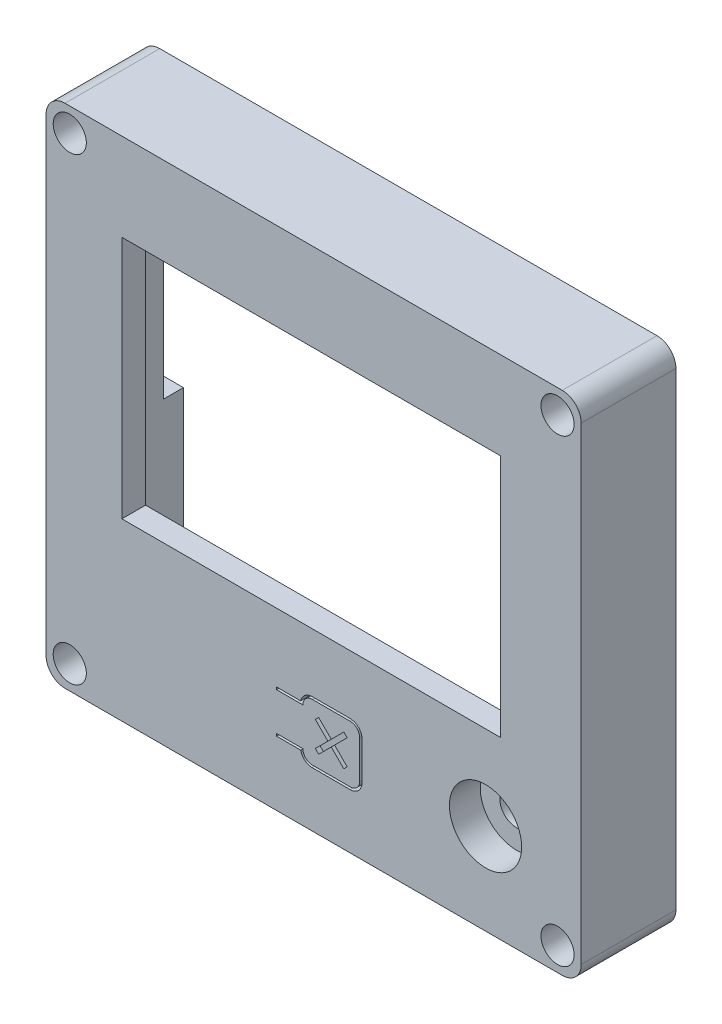
SolidWorks part; units mm, degrees
ref_plane "Front Plane" through (0, 0, 0) normal (0, 0, 1) x (1, 0, 0)
ref_plane "Top Plane" through (0, 0, 0) normal (0, 1, 0) x (1, 0, 0)
ref_plane "Right Plane" through (0, 0, 0) normal (1, 0, 0) x (0, 0, -1)
sketch "Sketch1" plane through (0, 0, 0) normal (0, 0, 1) x (1, 0, 0)
  line L1 (-56.5, -53.5) -> (56.5, -53.5)
  line L2 (-56.5, -53.5) -> (-56.5, 53.5)
  line L3 (-56.5, 53.5) -> (56.5, 53.5)
  line L4 (56.5, -53.5) -> (56.5, 53.5)
  line L5 (-56.5, -53.5) -> (56.5, 53.5) construction
  line L6 (-56.5, 53.5) -> (56.5, -53.5) construction
  point P0 (0, 0)
  dimension "D1" = 113
  dimension "D2" = 107
extrude "Main Body" add sketch "Sketch1" along normal blind 5
sketch "Sketch19" plane through (0, 0, 0) normal (0, 0, -1) x (-1, 0, 0)
  line L0 (-56.5, -53.5) -> (-56.5, 53.5) construction
  line L1 (-45.75, -43.75) -> (-27.25, -43.75)
  line L2 (-45.75, -43.75) -> (-45.75, -25.25)
  line L3 (-45.75, -25.25) -> (-27.25, -25.25)
  line L4 (-27.25, -43.75) -> (-27.25, -25.25)
  line L5 (-45.75, -43.75) -> (-27.25, -25.25) construction
  line L6 (-45.75, -25.25) -> (-27.25, -43.75) construction
  line L7 (56.5, -53.5) -> (-56.5, -53.5) construction
  circle A0 centre (-36.5, -34.5) radius 9.25 construction
  point P6 (0, 0)
  dimension "D1" = 18.5
  dimension "D2" = 18.5
  dimension "D3" = 18.5
  dimension "D4" = 20
  dimension "D5" = 19
extrude "Boss-Extrude1" add sketch "Sketch19" along normal blind 3
sketch "Sketch7" plane through (0, 0, 5) normal (0, 0, 1) x (1, 0, 0)
  line L0 (-56.5, 53.5) -> (-56.5, -53.5) construction
  line L1 (-40.5, 35) -> (39.5, 35)
  line L2 (-40.5, 35) -> (-40.5, -16.5)
  line L3 (-40.5, -16.5) -> (39.5, -16.5)
  line L4 (39.5, 35) -> (39.5, -16.5)
  line L5 (-40.5, 35) -> (39.5, -16.5) construction
  line L6 (-40.5, -16.5) -> (39.5, 35) construction
  line L7 (56.5, 53.5) -> (-56.5, 53.5) construction
  line L8 (56.5, -53.5) -> (56.5, 53.5) construction
  line L9 (-56.5, -53.5) -> (56.5, -53.5) construction
  line L10 (-56.5, -53.5) -> (56.5, -53.5) construction
  line L11 (0.71, -38.42) -> (6.7298, -38.42) construction
  line L12 (0.71, -38.42) -> (0.71, -32.4002) construction
  line L13 (0.71, -32.4002) -> (6.7298, -32.4002) construction
  line L14 (6.7298, -38.42) -> (6.7298, -32.4002) construction
  line L15 (0.71, -38.42) -> (6.7298, -32.4002) construction
  line L16 (0.71, -32.4002) -> (6.7298, -38.42) construction
  line L17 (-56.5, 53.5) -> (-56.5, -53.5) construction
  circle A0 centre (36.3, -34.31) radius 3.5
  circle A1 centre (3.7199, -35.4101) radius 3 construction
  point P0 (-0.5, 9.25)
  point P15 (3.7199, -35.4101)
  dimension "D5" = 7
  dimension "D12" = 6
  dimension "D1" = 51.5
  dimension "D2" = 80
  dimension "D3" = 16
  dimension "D4" = 18.5
  dimension "D6" = 20.2
  dimension "D7" = 19.19
  dimension "D8" = 6.0198
  dimension "D9" = 6.0198
  dimension "D10" = 18.0899
  dimension "D11" = 60.2199
extrude "Screen and knob locatation" cut sketch "Sketch7" against normal through all
sketch "Sketch11" plane through (0, 0, 0) normal (0, 0, -1) x (-1, 0, 0)
  line L1 (40.4022, -49.2813) -> (-27.252, -49.2813)
  line L2 (40.4022, -49.2813) -> (40.4022, -18.7536)
  line L3 (40.4022, -18.7536) -> (-27.252, -18.7536)
  line L4 (-27.252, -49.2813) -> (-27.252, -18.7536)
  line L5 (40.4022, -49.2813) -> (-27.252, -18.7536) construction
  line L6 (40.4022, -18.7536) -> (-27.252, -49.2813) construction
  point P0 (6.5751, -34.0175)
extrude "Internal cavity" cut sketch "Sketch11" against normal blind 3
sketch "Sketch12" plane through (0, 0, 0) normal (0, 0, -1) x (-1, 0, 0)
  line L0 (56.5, -53.5) -> (-56.5, -53.5) construction
  line L1 (56.5, 53.5) -> (46.5, 53.5)
  line L2 (56.5, 53.5) -> (56.5, -53.5)
  line L3 (56.5, -53.5) -> (46.5, -53.5)
  line L4 (47.5, 44.5) -> (47.5, -44.5)
  line L5 (-56.5, -53.5) -> (-56.5, 53.5) construction
  line L6 (56.5, -53.5) -> (-56.5, -53.5)
  line L7 (56.5, -53.5) -> (56.5, -43.5)
  line L8 (47.5, -44.5) -> (-47.5, -44.5)
  line L9 (-56.5, -53.5) -> (-56.5, -43.5)
  line L11 (-56.5, 53.5) -> (-46.5, 53.5)
  line L12 (-56.5, 53.5) -> (-56.5, -53.5)
  line L13 (-56.5, -53.5) -> (-46.5, -53.5)
  line L14 (-47.5, 44.5) -> (-47.5, -44.5)
  line L15 (56.5, 53.5) -> (-56.5, 53.5)
  line L16 (56.5, 53.5) -> (56.5, 43.5)
  line L17 (47.5, 44.5) -> (-47.5, 44.5)
  line L18 (-56.5, 53.5) -> (-56.5, 43.5)
  line M9 (-27.252, -49.2813) -> (-27.252, -43.75)
  line M11 (40.4022, -18.7536) -> (40.4022, -49.2813)
  line M12 (40.4022, -49.2813) -> (-27.252, -49.2813)
  line M22 (-56.5, 53.5) -> (-56.5, -53.5)
  line M23 (-56.5, -53.5) -> (56.5, -53.5)
  line M24 (56.5, -53.5) -> (56.5, 53.5)
  line M25 (56.5, 53.5) -> (-56.5, 53.5)
  dimension "D1" = 9
  dimension "D2" = 9
  dimension "D3" = 9
  dimension "D4" = 9
extrude "Boarders" add sketch "Sketch12" along normal blind 15 contours L12 L6 L2 L17 L4 L8 L14 M25 M22 M23 M24 M11 M12 M9 region at (-54.9438, 48.5, 0)
sketch "Sketch6" plane through (0, 0, 5) normal (0, 0, 1) x (1, 0, 0)
  line L0 (51.5, 48.5) -> (51.5, -48.5) construction
  line L1 (51.5, -48.5) -> (-51.5, -48.5) construction
  line L2 (-51.5, -48.5) -> (-51.5, 48.5) construction
  line L3 (-51.5, 48.5) -> (51.5, 48.5) construction
  line L4 (56.5, -53.5) -> (56.5, 53.5) construction
  line L5 (-56.5, 53.5) -> (-56.5, -53.5) construction
  line L6 (56.5, 53.5) -> (-56.5, 53.5) construction
  line L7 (-56.5, -53.5) -> (56.5, -53.5) construction
  circle A0 centre (-51.5, 48.5) radius 3.5
  circle A1 centre (-51.5, -48.5) radius 3.5
  circle A2 centre (51.5, -48.5) radius 3.5
  circle A3 centre (51.5, 48.5) radius 3.5
  dimension "D5" = 7
  dimension "D6" = 7
  dimension "D7" = 7
  dimension "D8" = 7
  dimension "D1" = 5
  dimension "D2" = 5
  dimension "D3" = 5
  dimension "D4" = 5
extrude "Screw Head Placement" cut sketch "Sketch6" against normal blind 15
sketch "Sketch10" plane through (0, 0, -10) normal (0, 0, 1) x (1, 0, 0)
  circle A0 centre (-51.5, 48.5) radius 1.6801
  circle A1 centre (51.5, 48.5) radius 1.6801
  circle A2 centre (51.5, -48.5) radius 1.6801
  circle A3 centre (-51.5, -48.5) radius 2
  dimension "D1" = 4
extrude "Screw hole through" cut sketch "Sketch10" against normal through all
sketch "Sketch14" plane through (-56.5, 0, 0) normal (-1, 0, 0) x (0, 0, 1)
  line L0 (5, 53.5) -> (-15, 53.5) construction
  line L1 (-15, 22) -> (-10.75, 22)
  line L2 (-15, 22) -> (-15, -6)
  line L3 (-15, -6) -> (-10.75, -6)
  line L4 (-10.75, 22) -> (-10.75, -6)
  line L5 (-15, 22) -> (-10.75, -6) construction
  line L6 (-15, -6) -> (-10.75, 22) construction
  line L7 (-15, -53.5) -> (-15, 53.5) construction
  point P0 (-12.875, 8)
  dimension "D1" = 28
  dimension "D2" = 4.25
  dimension "D3" = 31.5
extrude "SD Card Slot" cut sketch "Sketch14" against normal blind 10
sketch "Sketch15" plane through (0, 0, 3) normal (0, 0, -1) x (-1, 0, 0)
  circle A0 centre (-3.7199, -35.4101) radius 3
  dimension "D1" = 6
extrude "Button Press" add sketch "Sketch15" along normal blind 8.25
sketch "Sketch16" plane through (0, 0, 3) normal (0, 0, -1) x (-1, 0, 0)
  line L0 (2.2801, -39.4101) -> (7.8264, -39.4101)
  line L1 (-7.7199, -41.4101) -> (0.2801, -41.4101)
  line L2 (-9.7199, -39.4101) -> (-9.7199, -31.4101)
  line L3 (-7.7199, -29.4101) -> (0.2801, -29.4101)
  line L5 (-9.7199, -41.4101) -> (-9.1341, -40.8243) construction
  line L6 (-9.7199, -29.4101) -> (-9.1341, -29.9959) construction
  line L7 (7.8264, -31.4101) -> (2.2801, -31.4101)
  line L8 (7.8264, -39.4101) -> (7.8264, -31.4101) construction
  line L22 (7.8264, -30.9101) -> (2.7296, -30.9101)
  line L23 (-7.7199, -28.9101) -> (0.2801, -28.9101)
  line L24 (-10.2199, -39.4101) -> (-10.2199, -31.4101)
  line L25 (-7.7199, -41.9101) -> (0.2801, -41.9101)
  line L26 (2.7296, -39.9101) -> (7.8264, -39.9101)
  line L27 (7.8264, -39.9101) -> (7.8264, -39.4101)
  line L28 (7.8264, -31.4101) -> (7.8264, -30.9101)
  line L29 (1.6943, -29.9959) -> (2.2801, -29.4101) construction
  line L30 (1.6943, -40.8243) -> (2.2801, -41.4101) construction
  arc A0 (2.2801, -31.4101) -> (0.2801, -29.4101) centre (0.2801, -31.4101) ccw
  arc A1 (2.2801, -39.4101) -> (0.2801, -41.4101) centre (0.2801, -39.4101) cw
  arc A2 (-7.7199, -41.4101) -> (-9.7199, -39.4101) centre (-7.7199, -39.4101) cw
  arc A3 (-9.7199, -31.4101) -> (-7.7199, -29.4101) centre (-7.7199, -31.4101) cw
  arc A4 (2.7296, -30.9101) -> (0.2801, -28.9101) centre (0.2801, -31.4101) ccw
  arc A5 (-10.2199, -31.4101) -> (-7.7199, -28.9101) centre (-7.7199, -31.4101) cw
  arc A6 (-7.7199, -41.9101) -> (-10.2199, -39.4101) centre (-7.7199, -39.4101) cw
  arc A7 (2.7296, -39.9101) -> (0.2801, -41.9101) centre (0.2801, -39.4101) cw
  point P0 (-3.7199, -35.4101)
  dimension "D1" = 2
  dimension "D3" = 12
  dimension "D11" = 0.5
extrude "Groove Cut" cut sketch "Sketch16" against normal through all
sketch "Sketch17" plane through (0, 0, 5) normal (0, 0, 1) x (1, 0, 0)
  line L0 (0.71, -38.42) -> (6.7298, -32.4002) construction
  line L1 (0.71, -32.4002) -> (6.7298, -38.42) construction
  line L2 (0.3564, -32.7538) -> (3.0128, -35.4101)
  line L3 (1.0636, -32.0466) -> (3.7199, -34.703)
  line L4 (1.0636, -38.7736) -> (3.7199, -36.1172)
  line L5 (0.3564, -38.0664) -> (3.0128, -35.4101)
  line L6 (4.427, -35.4101) -> (7.0834, -38.0664)
  line L7 (1.0636, -32.0466) -> (7.0834, -38.0664) construction
  line L8 (3.7199, -34.703) -> (6.3762, -32.0466)
  line L9 (0.3564, -38.0664) -> (6.3762, -32.0466) construction
  line L10 (3.7199, -36.1172) -> (6.3762, -38.7736)
  line L11 (0.3564, -32.7538) -> (6.3762, -38.7736) construction
  line L12 (4.427, -35.4101) -> (7.0834, -32.7538)
  line L13 (1.0636, -38.7736) -> (7.0834, -32.7538) construction
  line L14 (0.3564, -32.7538) -> (1.0636, -32.0466)
  line L15 (6.3762, -32.0466) -> (7.0834, -32.7538)
  line L16 (7.0834, -38.0664) -> (6.3762, -38.7736)
  line L17 (1.0636, -38.7736) -> (0.3564, -38.0664)
  dimension "D1" = 0.5
  dimension "D2" = 0.5
  dimension "D3" = 0.5
  dimension "D4" = 0.5
extrude "CAncel Decal" cut sketch "Sketch17" against normal blind 1
fillet "Main Body Fillet" radius 4 4 edges at (-56.5, -53.5, -5) (56.5, -53.5, -5) (56.5, 53.5, -5) (-56.5, 53.5, -5)
sketch "Sketch18" plane through (0, 0, 5) normal (0, 0, 1) x (1, 0, 0)
  circle A0 centre (36.3, -34.31) radius 7.625
  dimension "D1" = 15.25
extrude "Cut-Extrude1" cut sketch "Sketch18" against normal blind 6.5
